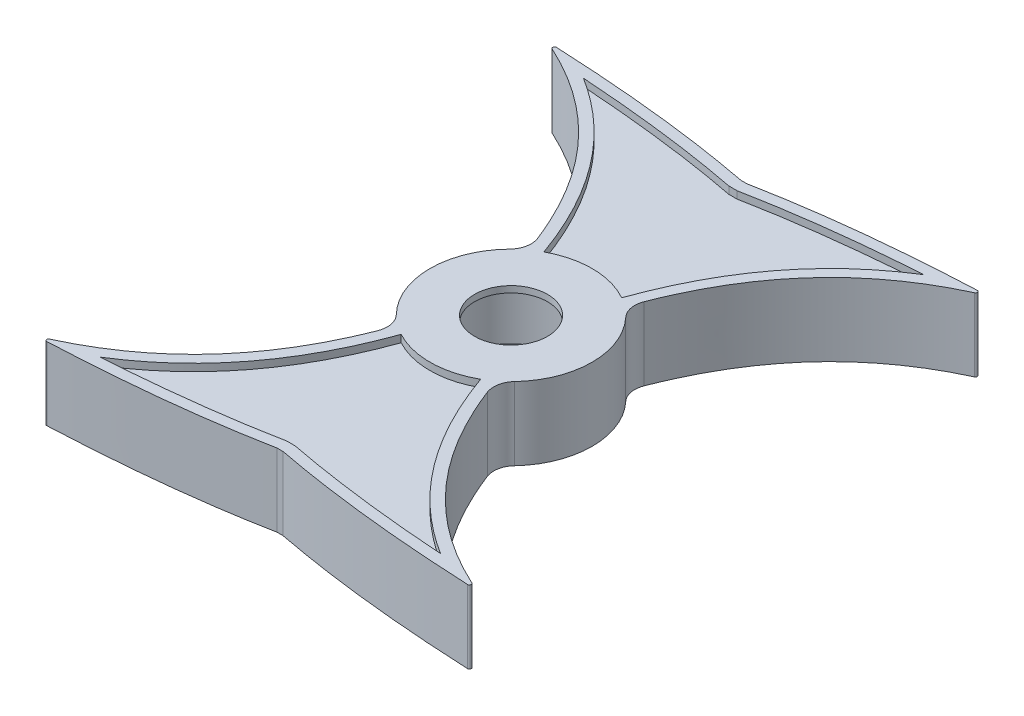
SolidWorks part; units mm, degrees
ref_plane "Front Plane" through (0, 0, 0) normal (0, 0, 1) x (1, 0, 0)
ref_plane "Top Plane" through (0, 0, 0) normal (0, 1, 0) x (1, 0, 0)
ref_plane "Right Plane" through (0, 0, 0) normal (1, 0, 0) x (0, 0, -1)
sketch "Sketch1" plane through (0, 0, 0) normal (0, 1, 0) x (1, 0, 0)
  line L0 (113.3347, 109.2847) -> (688.0014, 109.2847) construction
  line L1 (-30.0378, 69.9974) -> (30.2984, 69.9974) construction
  line L2 (0.1303, 66.7203) -> (0.1303, 0)
  line L3 (0.1303, 0) -> (0, 0)
  spline S0 degree 3 poles (-30.0378, 69.9974) (-1.599, 57.8695) (-2.4374, 25.039) (0, 0) knots 0 0 0 0 1 1 1 1
  spline S1 degree 3 poles (-30.0378, 69.9974) (-20.2712, 69.5991) (-9.7937, 68.6776) (0.1303, 66.7203) knots 0 0 0 0 1 1 1 1
  spline S2 degree 2 poles (-30.0378, 69.9974) (-13.5989, 68.4686) (0.1303, 60.6728) knots 0 0 0 1 1 1
  spline S3 degree 2 poles (-30.0378, 69.9974) (-8.5139, 65.1779) (0.1303, 48.9403) knots 0 0 0 1 1 1
  spline S4 degree 2 poles (-4.7975, 38.1052) (-2.8858, 43.7413) (0.1303, 48.9403) knots 0 0 0 1 1 1
  spline S5 degree 2 poles (-9.9544, 51.6606) (-5.8244, 57.0154) (0.1303, 60.6728) knots 0 0 0 1 1 1
  spline S6 degree 2 poles (0.1303, 66.7203) (-8.4881, 64.4255) (-16.4239, 60.6728) knots 0 0 0 1 1 1
  point P2 (-30.0378, 69.9974)
  point P3 (30.2984, 69.9974)
  point P5 (0.1303, 0)
  point P7 (0.1303, 69.9974)
  point P8 (0.1303, 66.7203)
  point P12 (0.1303, 48.9403)
  point P15 (0.1303, 60.6728)
  point P16 (-4.7975, 38.1052)
  point P17 (-9.9544, 51.6606)
  point P18 (-16.4239, 60.6728)
sketch "Sketch2" plane through (0, 0, 0) normal (0, 1, 0) x (1, 0, 0)
  line L0 (0.1303, 66.7203) -> (0.1303, 0) construction
  line L1 (0.1303, 66.7203) -> (0.1303, 0)
  line L2 (0, 0) -> (0.2606, 0)
  line L3 (-30.0378, 69.9974) -> (30.2984, 69.9974) construction
  line L4 (-30.0378, 69.9974) -> (-30.0378, 0) construction
  line L5 (-30.0378, 0) -> (30.2984, 0) construction
  line L6 (30.2984, 69.9974) -> (30.2984, 0) construction
  line L7 (-30.0378, 34.9987) -> (30.2984, 34.9987) construction
  parabola Q0 (-30.0378, 69.9974) -> (0.1303, 60.6728) focus (-21.2232, 31.0605) apex (-6.9037, 64.179) construction
  parabola Q1 (-30.0378, 69.9974) -> (0.1303, 48.9403) focus (-18.9027, 44.0178) apex (-4.9968, 56.3455) construction
  parabola Q2 (0.1303, 66.7203) -> (-16.4239, 60.6728) focus (4.203, 17.4746) apex (-16.0978, 60.8262) construction
  parabola Q3 (-9.9544, 51.6606) -> (0.1303, 60.6728) focus (5.5466, 41.8402) apex (-7.7753, 54.2319) construction
  parabola Q4 (-4.7975, 38.1052) -> (0.1303, 48.9403) focus (23.8856, 29.9476) apex (-3.7726, 40.8959) construction
  parabola Q5 (-30.0378, 69.9974) -> (0.1303, 60.6728) focus (-21.2232, 31.0605) apex (-6.9037, 64.179)
  parabola Q6 (-30.0378, 69.9974) -> (0.1303, 48.9403) focus (-18.9027, 44.0178) apex (-4.9968, 56.3455)
  parabola Q7 (0.1303, 66.7203) -> (-16.4239, 60.6728) focus (4.203, 17.4746) apex (-16.0978, 60.8262)
  parabola Q8 (-9.9544, 51.6606) -> (0.1303, 60.6728) focus (5.5466, 41.8402) apex (-7.7753, 54.2319)
  parabola Q9 (-4.7975, 38.1052) -> (0.1303, 48.9403) focus (23.8856, 29.9476) apex (-3.7726, 40.8959)
  parabola Q10 (5.058, 38.1052) -> (0.1303, 48.9403) focus (-23.6251, 29.9476) apex (4.0332, 40.8959)
  parabola Q11 (10.2149, 51.6606) -> (0.1303, 60.6728) focus (-5.286, 41.8402) apex (8.0359, 54.2319)
  parabola Q12 (0.1303, 66.7203) -> (16.6845, 60.6728) focus (-3.9424, 17.4746) apex (16.3584, 60.8262)
  parabola Q13 (30.2984, 69.9974) -> (0.1303, 48.9403) focus (19.1633, 44.0178) apex (5.2573, 56.3455)
  parabola Q14 (30.2984, 69.9974) -> (0.1303, 60.6728) focus (21.4838, 31.0605) apex (7.1643, 64.179)
  spline S0 degree 3 poles (-3322.8099, -2185.7853) (3186.4202, 2831.7954) (-3095.8991, -2931.9457) (3042.393, 2591.51) knots -3.759918 -3.759918 -3.759918 -3.759918 5.423547 5.423547 5.423547 5.423547 only from (-30.0378, 69.9974) to (0, 0) construction
  spline S1 degree 3 poles (3777.074, 1296.1317) (-4266.9385, -1405.0061) (4079.0466, 1836.1836) (-3383.0002, -2033.7274) knots -14.414394 -14.414394 -14.414394 -14.414394 15.007105 15.007105 15.007105 15.007105 only from (-30.0378, 69.9974) to (0.1303, 66.7203) construction
  spline S2 degree 3 poles (-30.0378, 69.9974) (-1.599, 57.8695) (-2.4374, 25.039) (0, 0) knots 0 0 0 0 1 1 1 1
  spline S3 degree 3 poles (-30.0378, 69.9974) (-20.2712, 69.5991) (-9.7937, 68.6776) (0.1303, 66.7203) knots 0 0 0 0 1 1 1 1
  spline S4 degree 3 poles (30.2984, 69.9974) (20.5318, 69.5991) (10.0543, 68.6776) (0.1303, 66.7203) knots 0 0 0 0 1 1 1 1
  spline S5 degree 3 poles (30.2984, 69.9974) (1.8596, 57.8695) (2.698, 25.039) (0.2606, 0) knots 0 0 0 0 1 1 1 1
sketch "Sketch3" plane through (0, 0, 0) normal (0, 1, 0) x (1, 0, 0)
  line L0 (-30.0378, 34.9987) -> (30.2984, 34.9987) construction
  line L1 (-30.0378, 34.9987) -> (30.2984, 34.9987) construction
  line L2 (0.1303, 66.7203) -> (0.1303, 0) construction
  line L3 (0.1303, 66.7203) -> (0.1303, 0) construction
  line L4 (0, 69.9974) -> (0.2606, 69.9974)
  parabola Q0 (0.1303, 3.2771) -> (16.6845, 9.3246) focus (-3.9424, 52.5228) apex (16.3584, 9.1712)
  parabola Q18 (5.058, 31.8923) -> (0.1303, 21.0571) focus (-23.6251, 40.0498) apex (4.0332, 29.1015)
  parabola Q19 (-4.7975, 31.8923) -> (0.1303, 21.0571) focus (23.8856, 40.0498) apex (-3.7726, 29.1015)
  parabola Q20 (-30.0378, 0) -> (0.1303, 21.0571) focus (-18.9027, 25.9796) apex (-4.9968, 13.652)
  parabola Q21 (30.2984, 0) -> (0.1303, 21.0571) focus (19.1633, 25.9796) apex (5.2573, 13.652)
  parabola Q22 (30.2984, 0) -> (0.1303, 9.3246) focus (21.4838, 38.9369) apex (7.1643, 5.8184)
  parabola Q23 (10.2149, 18.3368) -> (0.1303, 9.3246) focus (-5.286, 28.1572) apex (8.0359, 15.7655)
  parabola Q24 (-9.9544, 18.3368) -> (0.1303, 9.3246) focus (5.5466, 28.1572) apex (-7.7753, 15.7655)
  parabola Q25 (-30.0378, 0) -> (0.1303, 9.3246) focus (-21.2232, 38.9369) apex (-6.9037, 5.8184)
  parabola Q26 (0.1303, 3.2771) -> (-16.4239, 9.3246) focus (4.203, 52.5228) apex (-16.0978, 9.1712)
  spline S8 degree 3 poles (-30.0378, 0) (-1.599, 12.1279) (-2.4374, 44.9584) (0, 69.9974) knots 0 0 0 0 1 1 1 1
  spline S9 degree 3 poles (30.2984, 0) (1.8596, 12.1279) (2.698, 44.9584) (0.2606, 69.9974) knots 0 0 0 0 1 1 1 1
  spline S10 degree 3 poles (-30.0378, 0) (-20.2712, 0.3983) (-9.7937, 1.3198) (0.1303, 3.2771) knots 0 0 0 0 1 1 1 1
  spline S11 degree 3 poles (30.2984, 0) (20.5318, 0.3983) (10.0543, 1.3198) (0.1303, 3.2771) knots 0 0 0 0 1 1 1 1
extrude "Boss-Extrude1" add sketch "Sketch2" against normal mid plane 10 contours S5 Q10 L1 L2 | Q9 S2 L2 L1 | Q8 S2 Q9 Q6 | Q8 Q6 L1 | Q13 Q11 L1 | S5 Q11 Q13 Q10 | S5 Q12 Q13 Q11 | Q12 Q14 Q11 Q13 | S5 Q13 Q12 | Q13 Q14 Q12 | Q14 S4 Q12 | Q14 Q12 L1 | L1 Q7 Q5 | Q6 Q8 Q5 Q7 | Q7 S2 Q8 Q6 | Q6 S2 Q7 | Q7 Q5 Q6 | S3 Q5 Q7 region at (2.6261, 0, -63.9995) region at (-2.3656, 0, -63.9995) region at (11.4004, 0, -67.2893) region at (-11.1398, 0, -67.2893) region at (1.9065, 0, -55.6514) region at (-5.9249, 0, -60.9685) region at (-1.646, 0, -55.6514) region at (6.1854, 0, -60.9685) region at (-15.931, 0, -66.1003) region at (16.1916, 0, -66.1003) region at (-19.0374, 0, -64.8341) region at (19.298, 0, -64.8341) region at (1.6366, 0, -30.3193) region at (-4.856, 0, -48.7633) region at (-1.3761, 0, -30.3193) region at (5.1165, 0, -48.7633) region at (-10.6687, 0, -57.7542) region at (10.9293, 0, -57.7542)
extrude "Boss-Extrude2" add sketch "Sketch3" against normal mid plane 10 contours Q18 S9 L4 S8 Q19 | S8 Q24 Q20 Q19 | Q23 S9 Q18 Q21 | Q20 Q24 Q23 Q21 | Q0 S9 Q23 Q21 | Q21 Q23 Q22 Q0 | Q21 S9 Q0 | Q22 Q21 Q0 | S11 Q22 Q0 | Q26 Q0 Q22 Q25 | Q26 Q25 Q24 Q20 | S8 Q26 Q20 Q24 | S8 Q20 Q26 | Q25 Q26 Q20 | Q25 S10 Q26 region at (0.1303, 0, -39.6781) region at (-4.856, 0, -21.2341) region at (5.1165, 0, -21.2341) region at (0.1303, 0, -14.346) region at (-10.6687, 0, -12.2432) region at (10.9293, 0, -12.2432) region at (-5.9249, 0, -9.0289) region at (6.1854, 0, -9.0289) region at (-19.0374, 0, -5.1633) region at (19.298, 0, -5.1633) region at (-15.931, 0, -3.8972) region at (0.1303, 0, -5.9979) region at (16.1916, 0, -3.8972) region at (-11.1398, 0, -2.7081) region at (11.4004, 0, -2.7081)
sketch "Sketch14" plane through (0, 5, 0) normal (0, 1, 0) x (1, 0, 0)
  line L0 (-0.2922, 66.8029) -> (0.5528, 66.8029)
  line L1 (-0.2922, 3.1945) -> (0.5528, 3.1945)
  line L2 (0.2606, 69.9974) -> (0, 69.9974)
  line L3 (0, 0) -> (0.2606, 0)
  line L6 (-0.4364, 65.3029) -> (0.6969, 65.3029)
  line L7 (-0.4364, 4.6945) -> (0.6969, 4.6945)
  spline S0 degree 1 poles (23.4682, 68.1304) (0.6969, 65.3029) knots 0 0 1 1 construction
  spline S1 degree 1 poles (2.779, 34.9987) (23.4682, 68.1304) knots 0 0 1 1 construction
  spline S2 degree 1 poles (23.4682, 1.867) (2.779, 34.9987) knots 0 0 1 1 construction
  spline S3 degree 1 poles (0.6969, 4.6945) (23.4682, 1.867) knots 0 0 1 1 construction
  spline S4 degree 1 poles (-23.2077, 1.867) (-0.4364, 4.6945) knots 0 0 1 1 construction
  spline S5 degree 1 poles (-2.5185, 34.9987) (-23.2077, 1.867) knots 0 0 1 1 construction
  spline S6 degree 1 poles (-23.2077, 68.1304) (-2.5185, 34.9987) knots 0 0 1 1 construction
  spline S7 degree 1 poles (-0.4364, 65.3029) (-23.2077, 68.1304) knots 0 0 1 1 construction
  spline S8 degree 3 poles (0.6969, 65.3029) (2.5696, 65.6662) (6.318, 66.3195) (12.0394, 67.1017) (17.7828, 67.7067) (21.5677, 68.0034) (23.4682, 68.1304) knots 0.233116 0.233116 0.233116 0.233116 0.422479 0.611841 0.801203 0.990565 0.990565 0.990565 0.990565
  spline S9 degree 3 poles (23.4682, 68.1304) (22.7121, 67.6565) (21.2175, 66.6514) (18.4608, 64.5237) (15.3623, 61.6102) (12.1857, 57.771) (8.6057, 52.2547) (5.9209, 46.2373) (3.9276, 39.8942) (3.1389, 36.6324) (2.779, 34.9987) knots -0.004075 -0.004075 -0.004075 -0.004075 0.026512 0.057099 0.118273 0.179447 0.240622 0.36297 0.424144 0.485318 0.485318 0.485318 0.485318
  spline S10 degree 3 poles (2.779, 34.9987) (3.1389, 33.365) (3.9276, 30.1032) (5.9209, 23.7601) (8.6057, 17.7427) (12.1857, 12.2264) (15.3623, 8.3872) (18.4608, 5.4737) (21.2175, 3.346) (22.7121, 2.3409) (23.4682, 1.867) knots 0.076587 0.076587 0.076587 0.076587 0.137762 0.198936 0.321284 0.382458 0.443632 0.504806 0.535393 0.56598 0.56598 0.56598 0.56598
  spline S11 degree 3 poles (23.4682, 1.867) (21.5677, 1.994) (17.7828, 2.2907) (12.0394, 2.8957) (6.318, 3.6779) (2.5696, 4.3312) (0.6969, 4.6945) knots -0.004745 -0.004745 -0.004745 -0.004745 0.184617 0.373979 0.563341 0.752703 0.752703 0.752703 0.752703
  spline S12 degree 3 poles (-2828.2703, 979.8669) (3288.6228, -1043.4993) (-3120.8336, 1425.1857) (2498.1897, -1568.8704) knots -13.150411 -13.150411 -13.150411 -13.150411 13.729882 13.729882 13.729882 13.729882 only from (30.2984, 69.9974) to (0.5528, 66.8029)
  spline S13 degree 3 poles (914.575, 472.4666) (-849.9272, -729.9232) (817.0336, 899.283) (-805.2261, -522.6125) knots -2.118312 -2.118312 -2.118312 -2.118312 3.791964 3.791964 3.791964 3.791964 only from (0.5528, 66.8029) to (0.2606, 69.9974)
  spline S14 degree 3 poles (805.4881, -522.6138) (-816.7728, 899.283) (850.1858, -729.9212) (-914.3105, 472.4639) knots -1.833971 -1.833971 -1.833971 -1.833971 4.076302 4.076302 4.076302 4.076302 only from (0, 69.9974) to (-0.2922, 66.8029)
  spline S15 degree 3 poles (-2497.9846, -1568.9) (3121.1447, 1425.2064) (-3288.4014, -1043.5133) (2828.5581, 979.8759) knots -12.744151 -12.744151 -12.744151 -12.744151 14.13627 14.13627 14.13627 14.13627 only from (-0.2922, 66.8029) to (-30.0378, 69.9974)
  spline S16 degree 3 poles (-2528.3963, -1578.6473) (2417.184, 2163.6636) (-2347.7237, -2248.2109) (2311.4239, 1934.4335) knots -3.351705 -3.351705 -3.351705 -3.351705 5.025052 5.025052 5.025052 5.025052 only from (-30.0378, 69.9974) to (-4.0544, 34.9987)
  spline S17 degree 3 poles (2311.4509, -1864.4603) (-2347.7371, 2318.2209) (2417.1832, -2093.6638) (-2528.3802, 1648.6325) knots -4.463163 -4.463163 -4.463163 -4.463163 3.913602 3.913602 3.913602 3.913602 only from (-4.0544, 34.9987) to (-30.0378, 0)
  spline S18 degree 3 poles (2828.5308, -909.8695) (-3288.3622, 1113.4967) (3121.0941, -1355.1883) (-2497.9291, 1638.8678) knots -13.150411 -13.150411 -13.150411 -13.150411 13.729882 13.729882 13.729882 13.729882 only from (-30.0378, 0) to (-0.2922, 3.1945)
  spline S19 degree 3 poles (-914.3144, -402.4692) (850.1878, 799.9206) (-816.773, -829.2856) (805.4866, 592.6099) knots -2.118312 -2.118312 -2.118312 -2.118312 3.791964 3.791964 3.791964 3.791964 only from (-0.2922, 3.1945) to (0, 0)
  spline S20 degree 3 poles (-805.2279, 592.6115) (817.0337, -829.2858) (-849.9256, 799.9189) (914.5714, -402.4667) knots -1.833971 -1.833971 -1.833971 -1.833971 4.076302 4.076302 4.076302 4.076302 only from (0.2606, 0) to (0.5528, 3.1945)
  spline S21 degree 3 poles (2498.2451, 1638.8974) (-3120.8841, -1355.209) (3288.662, 1113.5107) (-2828.2975, -909.8785) knots -12.744151 -12.744151 -12.744151 -12.744151 14.13627 14.13627 14.13627 14.13627 only from (0.5528, 3.1945) to (30.2984, 0)
  spline S22 degree 3 poles (2528.6569, 1648.6447) (-2416.9234, -2093.6661) (2347.9843, 2318.2083) (-2311.1632, -1864.436) knots -3.351705 -3.351705 -3.351705 -3.351705 5.025052 5.025052 5.025052 5.025052 only from (30.2984, 0) to (4.315, 34.9987)
  spline S23 degree 3 poles (-2311.1904, 1934.4578) (2347.9977, -2248.2235) (-2416.9227, 2163.6612) (2528.6408, -1578.6351) knots -4.463163 -4.463163 -4.463163 -4.463163 3.913602 3.913602 3.913602 3.913602 only from (4.315, 34.9987) to (30.2984, 69.9974)
  spline S24 degree 3 poles (30.2984, 69.9974) (20.6703, 69.6047) (10.3513, 68.7036) (0.5528, 66.8029) knots 0 0 0 0 0.98582 0.98582 0.98582 0.98582
  spline S25 degree 3 poles (-0.4364, 4.6945) (-2.309, 4.3312) (-6.0575, 3.6779) (-11.7789, 2.8957) (-17.5222, 2.2907) (-21.3072, 1.994) (-23.2077, 1.867) knots 0.233116 0.233116 0.233116 0.233116 0.422479 0.611841 0.801203 0.990565 0.990565 0.990565 0.990565
  spline S26 degree 3 poles (-23.2077, 1.867) (-22.4515, 2.3409) (-20.957, 3.346) (-18.2002, 5.4737) (-15.1017, 8.3872) (-11.9251, 12.2264) (-8.3452, 17.7427) (-5.6603, 23.7601) (-3.667, 30.1032) (-2.8783, 33.365) (-2.5185, 34.9987) knots -0.004075 -0.004075 -0.004075 -0.004075 0.026512 0.057099 0.118273 0.179447 0.240622 0.36297 0.424144 0.485318 0.485318 0.485318 0.485318
  spline S27 degree 3 poles (-0.2922, 66.8029) (-10.0907, 68.7036) (-20.4097, 69.6047) (-30.0378, 69.9974) knots 0 0 0 0 0.98582 0.98582 0.98582 0.98582
  spline S28 degree 3 poles (-30.0378, 69.9974) (-14.0579, 63.1827) (-7.3219, 49.8314) (-4.0544, 34.9987) knots 0 0 0 0 0.561905 0.561905 0.561905 0.561905
  spline S29 degree 3 poles (-4.0544, 34.9987) (-7.3219, 20.1661) (-14.0579, 6.8147) (-30.0378, 0) knots 0 0 0 0 0.561905 0.561905 0.561905 0.561905
  spline S30 degree 3 poles (-30.0378, 0) (-20.4097, 0.3927) (-10.0907, 1.2938) (-0.2922, 3.1945) knots 0 0 0 0 0.98582 0.98582 0.98582 0.98582
  spline S31 degree 3 poles (-2.5185, 34.9987) (-2.8783, 36.6324) (-3.667, 39.8942) (-5.6603, 46.2373) (-8.3452, 52.2547) (-11.9251, 57.771) (-15.1017, 61.6102) (-18.2002, 64.5237) (-20.957, 66.6514) (-22.4515, 67.6565) (-23.2077, 68.1304) knots 0.076587 0.076587 0.076587 0.076587 0.137762 0.198936 0.321284 0.382458 0.443632 0.504806 0.535393 0.56598 0.56598 0.56598 0.56598
  spline S32 degree 3 poles (-23.2077, 68.1304) (-21.3072, 68.0034) (-17.5222, 67.7067) (-11.7789, 67.1017) (-6.0575, 66.3195) (-2.309, 65.6662) (-0.4364, 65.3029) knots -0.004745 -0.004745 -0.004745 -0.004745 0.184617 0.373979 0.563341 0.752703 0.752703 0.752703 0.752703
  spline S33 degree 3 poles (0.5528, 3.1945) (10.3513, 1.2938) (20.6703, 0.3927) (30.2984, 0) knots 0 0 0 0 0.98582 0.98582 0.98582 0.98582
  spline S34 degree 3 poles (30.2984, 0) (14.3185, 6.8147) (7.5825, 20.1661) (4.315, 34.9987) knots 0 0 0 0 0.561905 0.561905 0.561905 0.561905
  spline S35 degree 3 poles (4.315, 34.9987) (7.5825, 49.8314) (14.3185, 63.1827) (30.2984, 69.9974) knots 0 0 0 0 0.561905 0.561905 0.561905 0.561905
  dimension "D1" = 0
  dimension "D2" = 1.5
extrude "Cut-Extrude2" cut sketch "Sketch14" against normal blind 1 contours S32 S31 S26 S25 L7 S11 S10 S9 S8 L6 region at (0.1303, 5, -34.9987)
sketch "Sketch15" plane through (0, 5, 0) normal (0, 1, 0) x (1, 0, 0)
  line L0 (-0.2922, 66.8029) -> (0.5528, 66.8029)
  line L1 (-0.2922, 3.1945) -> (0.5528, 3.1945)
  line L2 (-30.0378, 0) -> (30.2984, 0)
  line L3 (-30.0378, 69.9974) -> (30.2984, 69.9974)
  spline S0 degree 3 poles (-1877.9565, -598.7366) (2298.4513, 752.2946) (-2153.6741, -938.5934) (1619.5886, 1161.3607) knots -11.57699 -11.57699 -11.57699 -11.57699 12.134309 12.134309 12.134309 12.134309 only from (30.2984, 0) to (0.5528, 3.1945) construction
  spline S1 degree 3 poles (1878.217, -598.7366) (-2298.1907, 752.2946) (2153.9347, -938.5934) (-1619.328, 1161.3607) knots -11.57699 -11.57699 -11.57699 -11.57699 12.134309 12.134309 12.134309 12.134309 only from (-30.0378, 0) to (-0.2922, 3.1945) construction
  spline S2 degree 3 poles (-1877.9565, 668.734) (2298.4513, -682.2972) (-2153.6741, 1008.5909) (1619.5886, -1091.3633) knots -11.57699 -11.57699 -11.57699 -11.57699 12.134309 12.134309 12.134309 12.134309 only from (30.2984, 69.9974) to (0.5528, 66.8029) construction
  spline S3 degree 3 poles (1878.2171, 668.734) (-2298.1908, -682.2972) (2153.9347, 1008.5909) (-1619.3281, -1091.3633) knots -11.57699 -11.57699 -11.57699 -11.57699 12.134309 12.134309 12.134309 12.134309 only from (-30.0378, 69.9974) to (-0.2922, 66.8029) construction
  spline S4 degree 3 poles (30.2984, 0) (20.6703, 0.3927) (10.3513, 1.2938) (0.5528, 3.1945) knots 0 0 0 0 0.98582 0.98582 0.98582 0.98582
  spline S5 degree 3 poles (-30.0378, 0) (-20.4097, 0.3927) (-10.0907, 1.2938) (-0.2922, 3.1945) knots 0 0 0 0 0.98582 0.98582 0.98582 0.98582
  spline S6 degree 3 poles (30.2984, 69.9974) (20.6703, 69.6047) (10.3513, 68.7036) (0.5528, 66.8029) knots 0 0 0 0 0.98582 0.98582 0.98582 0.98582
  spline S7 degree 3 poles (-30.0378, 69.9974) (-20.4097, 69.6047) (-10.0907, 68.7036) (-0.2922, 66.8029) knots 0 0 0 0 0.98582 0.98582 0.98582 0.98582
extrude "Cut-Extrude3" cut sketch "Sketch15" against normal through all both and the other way through all
fillet "Fillet1" radius 0.25 4 edges
extrude "Cut-Extrude4" cut sketch "Sketch14<3>" along normal blind 1 from surface contours S32 S31 S26 S25 L7 S11 S10 S9 S8 L6 region at (0.1303, 5, -34.9987) starting at face at (0.1303, -5, -34.9987)
sketch "Sketch14<3>" plane through (0, 5, 0) normal (0, 1, 0) x (1, 0, 0) same geometry as "Sketch14"
sketch "Sketch16" plane through (0, 0, 0) normal (0, 1, 0) x (1, 0, 0)
  circle A0 centre (0, 34.9987) radius 8.125
  circle A1 centre (0, 34.9987) radius 11.125
  circle A2 centre (0, 34.9987) radius 5
  dimension "D1" = 16.25
  dimension "D3" = 10
  dimension "D2" = 3
extrude "Boss-Extrude3" add sketch "Sketch16" against normal mid plane 10 contours A1
fillet "Fillet2" radius 3 4 edges at (6.7851, 0, -43.8151) (6.7851, 0, -26.1823) (-6.579, 0, -43.9699) (-6.579, 0, -26.0275)
extrude "Cut-Extrude5" cut sketch "Sketch16<3>" against normal mid plane 8.25 contours A0 | A2 region at (-7.8952, 0, -34.9987) region at (0, 0, -34.9987)
sketch "Sketch16<3>" plane through (0, 0, 0) normal (0, 1, 0) x (1, 0, 0) same geometry as "Sketch16"
extrude "Cut-Extrude6" cut sketch "Sketch16<4>" against normal through all both and the other way through all contours A2 region at (0, 0, -34.9987)
sketch "Sketch16<4>" plane through (0, 0, 0) normal (0, 1, 0) x (1, 0, 0) same geometry as "Sketch16"
